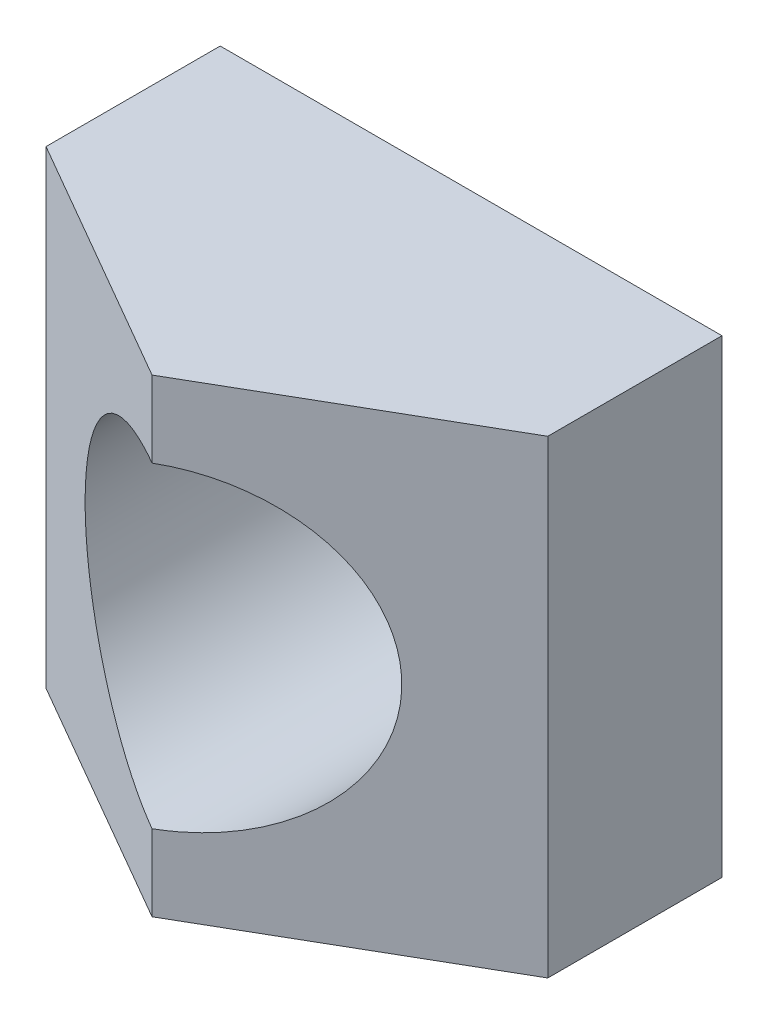
SolidWorks part; units mm, degrees
note: '?' marks a value the reader was unsure of.
material "RCH1000"
ref_plane "xy" through (0, 0, 0) normal (0, 0, 1) x (1, 0, 0)
ref_plane "xz" through (0, 0, 0) normal (0, 1, 0) x (1, 0, 0)
ref_plane "yz" through (0, 0, 0) normal (1, 0, 0) x (0, 0, -1)
ref_axis "x" through (-88.99, 0, 0) along (1, 0, 0)?
ref_axis "y" through (0, 55, 0) along (0, -1, 0)?
ref_axis "z" through (0, 0, -88.99) along (0, 0, 1)?
sketch "Sketch1" plane through (0, 0, 0) normal (0, 1, 0) x (1, 0, 0)
  line L1 (4.2782, -2.47) -> (4.2782, 2.47)
  line L2 (4.2782, 2.47) -> (0, 4.94)
  line L3 (0, 4.94) -> (-4.2782, 2.47)
  line L4 (-4.2782, 2.47) -> (-4.2782, -2.47)
  line L5 (-4.2782, -2.47) -> (0, -4.94)
  line L6 (0, -4.94) -> (4.2782, -2.47)
  circle A0 centre (0, 0) radius 4.2782 construction
  dimension "D1" = 4.94
extrude "Boss-Extrude1" add sketch "Sketch1" along normal mid plane 8
ref_plane "Plane1" through (0, 0, -0.5) normal (0, 0, 1) x (1, 0, 0)
other "SurfaceCut1"
sketch "Sketch2" plane through (0, 0, 0) normal (0, 0, 1) x (1, 0, 0)
  circle A0 centre (0, 0) radius 2.7
  dimension "D1" = 5.4
extrude "Cut-Extrude2" cut sketch "Sketch2" along normal through all and the other way through all
